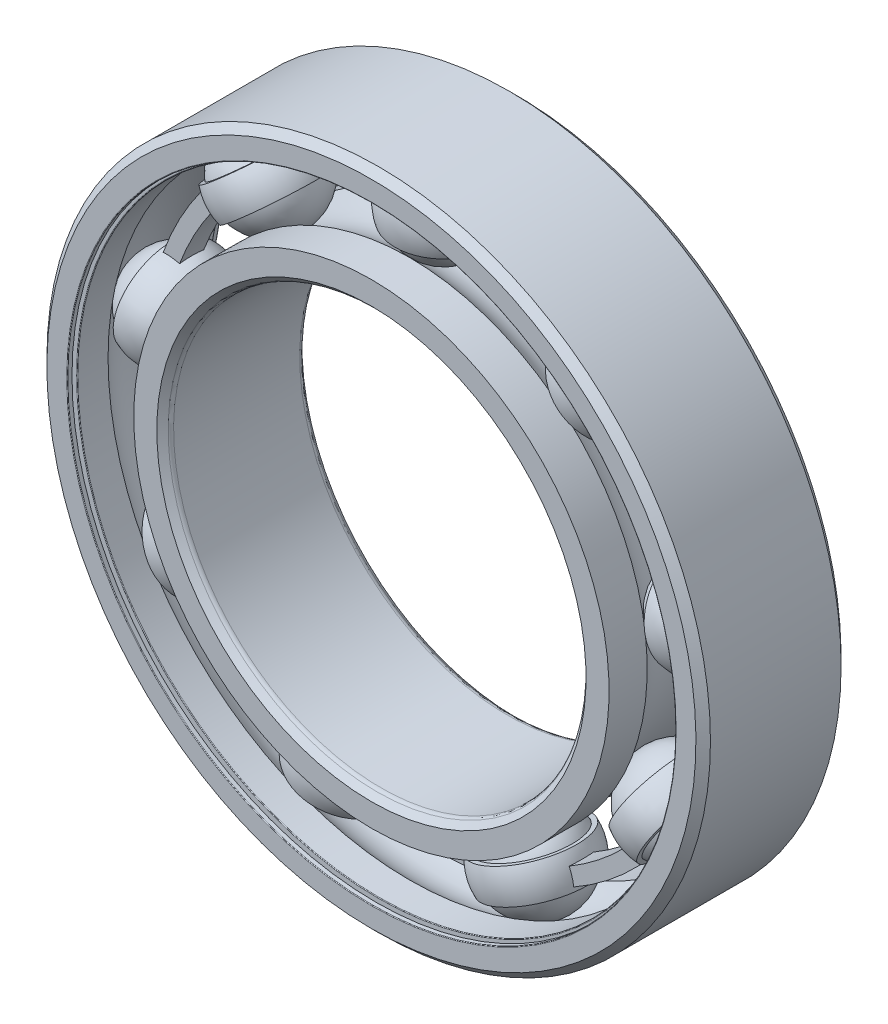
SolidWorks part; units mm, degrees
ref_plane "Front Plane" through (0, 0, 0) normal (0, 0, 1) x (1, 0, 0)
ref_plane "Top Plane" through (0, 0, 0) normal (0, 1, 0) x (1, 0, 0)
ref_plane "Right Plane" through (0, 0, 0) normal (1, 0, 0) x (0, 0, -1)
sketch "Sketch1" plane through (0, 0, 0) normal (0, 0, 1) x (1, 0, 0)
  line L0 (-16, 0) -> (16, 0) construction
  line L1 (-10, 0) -> (10, 0) construction
  circle A0 centre (0, 0) radius 10 construction
  circle A1 centre (0, 0) radius 16 construction
  point P3 (0, 0)
  point P6 (0, 0)
  point P7 (0, -10)
  point P11 (0, -16)
  point P12 (0, 10)
  point P13 (0, 16)
  dimension "OD" = 32
  dimension "ID" = 20
sketch "Sketch2" plane through (0, 0, 0) normal (1, 0, 0) x (0, 0, -1)
  line L0 (-3.5, 16) -> (3.5, 16) construction
  line L1 (0, 16) -> (0, -16) construction
  line L2 (3.15, 16) -> (-3.15, 16)
  line L3 (-3.15, 16) -> (-3.5, 15.65)
  line L4 (-3.5, 15.65) -> (-3.5, 14.5385)
  line L5 (-3.5, 14.5385) -> (-1.6625, 14.5385)
  line L6 (3.5, 14.5385) -> (1.6625, 14.5385)
  line L7 (3.5, 15.65) -> (3.5, 14.5385)
  line L8 (3.15, 16) -> (3.5, 15.65)
  line L9 (0, 16) -> (0, 13) construction
  line L10 (0, 13) -> (0, 10) construction
  line L11 (0, 16) -> (0, -16) construction
  line L12 (-3.5, 0) -> (3.5, 0) construction
  line L13 (3.5, 10) -> (-3.5, 10) construction
  line L14 (0, 15.2651) -> (0, 10.7349) construction
  line L15 (-3.5, -10) -> (3.5, -10) construction
  line L16 (-3.5, -10) -> (-3.5, 10) construction
  line L17 (3.5, 16) -> (3.5, -16) construction
  arc A0 (-1.6625, 14.5385) -> (1.6625, 14.5385) centre (0, 13) cw
  circle A1 centre (0, 13) radius 2.2651 construction
  point P14 (0, 10)
  point P17 (0, 0)
  point P21 (0, 16)
  point P29 (0, 10)
  point P30 (0, -10)
  point P35 (0, 15.2651)
  dimension "Approx. Ball Dia." = 4.5302
  dimension "Width" = 7
  dimension "D1" = 45
  dimension "D2" = 0.35
  dimension "D3" = 3.325
  dimension "D4" = 1.5385
  dimension "For Shaft Diameter" = 20
  dimension "For Housing ID" = 32
sketch "Sketch3" plane through (0, 0, 0) normal (1, 0, 0) x (0, 0, -1)
  line L0 (3.15, 16) -> (3.5, 15.65) construction
  line L1 (3.5, 15.65) -> (3.5, 14.5385) construction
  line L2 (3.5, 14.5385) -> (1.6625, 14.5385) construction
  line L3 (-3.5, 14.5385) -> (-1.6625, 14.5385) construction
  line L4 (-3.5, 15.65) -> (-3.5, 14.5385) construction
  line L5 (-3.15, 16) -> (-3.5, 15.65) construction
  line L6 (3.15, 16) -> (-3.15, 16) construction
  line L7 (3.15, 16) -> (3.5, 15.65)
  line L8 (3.5, 15.65) -> (3.5, 14.5385)
  line L9 (3.5, 14.5385) -> (1.6625, 14.5385)
  line L10 (-3.5, 14.5385) -> (-1.6625, 14.5385)
  line L11 (-3.5, 15.65) -> (-3.5, 14.5385)
  line L12 (-3.15, 16) -> (-3.5, 15.65)
  line L13 (3.15, 16) -> (-3.15, 16)
  arc A0 (1.6625, 14.5385) -> (-1.6625, 14.5385) centre (0, 13) ccw construction
  arc A1 (1.6625, 14.5385) -> (-1.6625, 14.5385) centre (0, 13) ccw
revolve "Revolve1" add sketch "Sketch3" angle 360 about L12
sketch "Sketch8" plane through (0, 0, 0) normal (1, 0, 0) x (0, 0, -1)
  line L0 (-3.5, 14.5385) -> (-1.6625, 14.5385) construction
  line L1 (-3.276, 14.5385) -> (-3.15, 14.5385)
  line L2 (-3.276, 14.5385) -> (-3.276, 15.0256) construction
  line L3 (-3.276, 15.0256) -> (-3.15, 15.0256)
  line L4 (-3.15, 14.5385) -> (-3.15, 15.0256)
  line L5 (3.5, 14.5385) -> (1.6625, 14.5385) construction
  line L6 (3.15, 14.5385) -> (3.276, 14.5385)
  line L7 (3.15, 14.5385) -> (3.15, 15.0256)
  line L8 (3.15, 15.0256) -> (3.276, 15.0256)
  line L9 (3.276, 14.5385) -> (3.276, 15.0256) construction
  line L10 (-3.15, 15.0256) -> (3.15, 15.0256) construction
  line L11 (0, 16) -> (0, -16) construction
  line L12 (-3.276, 15.0256) -> (-3.276, 15.5128) construction
  line L13 (-3.276, 15.5128) -> (-3.276, 16) construction
  line L14 (-3.5, 16) -> (3.5, 16) construction
  line L15 (-3.276, 14.5385) -> (-3.5, 14.5385)
  line L16 (-3.5, 14.5385) -> (-3.5, 14.6645)
  line L17 (-3.5, 15.65) -> (-3.5, 14.5385) construction
  line L18 (-3.5, 14.6645) -> (-3.276, 14.6645)
  line L19 (-3.276, 14.6645) -> (-3.276, 15.0256)
  line L20 (3.276, 14.5385) -> (3.5, 14.5385)
  line L21 (3.5, 14.5385) -> (3.5, 14.6645)
  line L22 (3.5, 15.65) -> (3.5, 14.5385) construction
  line L23 (3.5, 14.6645) -> (3.276, 14.6645)
  line L24 (3.276, 14.6645) -> (3.276, 15.0256)
  point P12 (0, 15.0256)
  dimension "D1" = 6.3
  dimension "D2" = 0.126
revolve "Cut-Revolve1" cut sketch "Sketch8" angle 360 about L12
sketch "Sketch4" plane through (0, 0, 0) normal (1, 0, 0) x (0, 0, -1)
  line L0 (0, 16) -> (0, -16) construction
  line L1 (0, 16) -> (0, -16) construction
  line L2 (-3.15, 10) -> (-3.5, 10.35)
  line L3 (-3.5, 10.35) -> (-3.5, 11.4615)
  line L5 (-3.5, 11.4615) -> (-1.6625, 11.4615)
  line L6 (-3.15, 10) -> (3.15, 10)
  line L8 (3.15, 10) -> (3.5, 10.35)
  line L10 (3.5, 10.35) -> (3.5, 11.4615)
  line L11 (3.5, 11.4615) -> (1.6625, 11.4615)
  line L12 (-3.5, 15.65) -> (-3.5, 14.5385) construction
  line L13 (3.15, 16) -> (3.5, 15.65) construction
  line L15 (3.5, -15.65) -> (3.5, 15.65) construction
  line L16 (3.15, 16) -> (3.15, -16) construction
  arc A1 (1.6625, 11.4615) -> (-1.6625, 11.4615) centre (0, 13) cw
  circle A2 centre (0, 13) radius 2.2651 construction
  point P1 (0, 10)
revolve "Revolve2" add sketch "Sketch4" angle 360 about L12
sketch "Sketch5" plane through (0, 0, 0) normal (1, 0, 0) x (0, 0, -1)
  line L0 (-2.2651, 13) -> (2.2651, 13)
  arc A2 (-2.2651, 13) -> (2.2651, 13) centre (0, 13) cw
  arc A3 (1.6625, 14.5385) -> (-1.6625, 14.5385) centre (0, 13) ccw construction
revolve "Revolve3" add sketch "Sketch5" angle 360 about L0
sketch "Sketch6" plane through (0, 0, 0) normal (1, 0, 0) x (0, 0, -1)
  line L0 (-1.6625, 14.5385) -> (-1.6625, 13.7692) construction
  line L1 (-1.6625, 13.7692) -> (-1.6625, 13) construction
  line L2 (-1.6625, 13) -> (-1.6625, 12.2308) construction
  line L3 (-1.6625, 12.2308) -> (-1.6625, 11.4615) construction
  line L4 (-3.5, 13.7692) -> (-3.2718, 13.7692) construction
  line L5 (-1.6625, 13.7692) -> (-1.6625, 12.2308) construction
  line L7 (-3.2718, 13.7692) -> (-3.0435, 13.7692) construction
  line L8 (-3.0435, 13.7692) -> (-2.8153, 13.7692) construction
  line L10 (0, 16) -> (0, -16) construction
  line L11 (0, 16) -> (0, -16) construction
  line L12 (-3.5, 14.5385) -> (-3.5, 13.7692) construction
  line L13 (-2.3588, 13.7692) -> (-2.1305, 13.7692) construction
  line L14 (-3.5, 15.65) -> (-3.5, -15.65) construction
  line L15 (-3.5, 13.7692) -> (-3.5, 13) construction
  line L16 (-3.5, 13) -> (-3.5, 12.2308) construction
  line L17 (-3.5, 12.2308) -> (-3.5, 11.4615) construction
  line L18 (-2.8153, 13.7692) -> (-2.587, 13.7692) construction
  line L19 (-2.587, 13.7692) -> (-2.3588, 13.7692) construction
  line L20 (-2.1305, 13.7692) -> (-2.3588, 13.7692)
  line L21 (-3.5, 12.2308) -> (-3.2718, 12.2308) construction
  line L22 (-3.2718, 12.2308) -> (-3.0435, 12.2308) construction
  line L23 (-3.0435, 12.2308) -> (-2.8153, 12.2308) construction
  line L24 (-2.8153, 12.2308) -> (-2.587, 12.2308) construction
  line L25 (-2.587, 12.2308) -> (-2.3588, 12.2308) construction
  line L26 (-2.3588, 12.2308) -> (-2.1305, 12.2308) construction
  line L27 (-2.1305, 12.2308) -> (-2.3588, 12.2308)
  line L28 (-2.587, 13.7692) -> (-2.587, 12.2308) construction
  line L30 (-2.4729, 13.7692) -> (-2.4729, 12.2308) construction
  circle A0 centre (0, 13) radius 2.2651 construction
  arc A2 (-2.3588, 12.2308) -> (-2.3588, 13.7692) centre (0.1766, 13) cw
  arc A3 (-2.1305, 13.7692) -> (-2.1305, 12.2308) centre (0, 13) ccw
revolve "Revolve4" add sketch "Sketch6" angle 360 about L11
sketch "Sketch7" plane through (0, 0, 0) normal (0, 0, 1) x (1, 0, 0)
  line L0 (-2.2651, 13) -> (2.2651, 13) construction
  line L1 (0, 10.7349) -> (0, 15.2651) construction
  line L2 (0, 0) -> (4.5056, 12.1943) construction
  line L8 (0, 16) -> (0, -16) construction
  line L9 (8.4526, 9.8769) -> (8.9528, 10.4613)
  line L10 (0, 16) -> (0, -16) construction
  line L11 (0, 13.7692) -> (0, 13)
  arc A1 (8.4526, 9.8769) -> (0, 13) centre (0, 0) ccw
  arc A2 (8.9528, 10.4613) -> (0, 13.7692) centre (0, 0) ccw
  dimension "D1" = 40.557
  dimension "D2" = 4.5302
extrude "Boss-Extrude1" add sketch "Sketch7" along normal mid plane 1.1667
pattern_circular "CirPattern1" count 9 over 360 about axis through (0, 0, 3.5) along (0, 0, -1) of bodies 104 134
pattern_circular "CirPattern2" count 9 over 360 about axis through (0, 0, 3.5) along (0, 0, -1) of "Revolve4", "Boss-Extrude1" reverse direction yes
fillet "Fillet1" radius 0.0315 4 edges at (0, -14.5385, -3.15) (0, -14.6645, -3.5) (0, -14.5385, 3.15) (0, -14.6645, 3.5)
fillet "Fillet2" radius 0.2625 2 edges at (0, -10, -3.15) (0, -10, 3.15)
ref_plane "Plane1" through (4.5056, 12.1943, 0) normal (0.3466, 0.938, 0) x (0.938, -0.3466, 0)
sketch "Sketch9" plane through (4.5056, 12.1943, 0) normal (0.3466, 0.938, 0) x (0.938, -0.3466, 0)
  line L0 (-2.3808, -0.5833) -> (-2.3808, -1.75)
  line L1 (-2.3808, -1.75) -> (-1.0327, -1.75)
  line L2 (-1.0327, -1.75) -> (0, -0.8834)
  line L3 (0, -0.8834) -> (1.0327, -1.75)
  line L4 (1.0327, -1.75) -> (2.3808, -1.75)
  line L5 (2.3808, -1.75) -> (2.3808, -0.5833)
  line L6 (2.3808, -0.5833) -> (-2.3808, -0.5833)
  line L7 (0, -0.5833) -> (0, 0) construction
  line L8 (-2.3808, -0.5833) -> (-2.3808, 0) construction
  dimension "D1" = 1.1667
  dimension "D2" = 0.5833
  dimension "D3" = 40
extrude "Boss-Extrude2" [suppressed] add sketch "Sketch9" along normal blind 1.982 draft 15 and the other way blind 1.982 draft 10 separate body draft outward yes other way draft outward yes
fillet "Fillet3" [suppressed] radius 0.35
mirror "Mirror1" [suppressed] about plane through (0, 0, 0) normal (0, 0, 1) of bodies 149
pattern_circular "CirPattern3" [suppressed] count 9 over 360 about axis through (0, 0, 3.5) along (0, 0, -1) of bodies 158 149
equation "\"D2@Sketch2\" = \"Width@Sketch2\" * .05"
equation "\"D3@Sketch2\"=\"Width@Sketch2\" * .475"
equation "\"D4@Sketch2\" =  (  (  ( \"OD@Sketch1\" - \"Width@Sketch2\" )  / 2 )  / 3.25 )  / 2.5"
equation "\"D1@Boss-Extrude1\" = \"Width@Sketch2\" / 6"
equation "\"D1@Sketch8\"=\"Width@Sketch2\"*.9"
equation "\"D2@Sketch8\"=\"D1@Sketch8\"*.02"
equation "\"D1@Fillet1\" = \"D2@Sketch8\" * .25"
equation "\"D1@Fillet2\" = \"D2@Sketch2\" * .75"
equation "\"Approx No of Balls\"= ( pi * \"OD@Sketch1\" ) * .4 / \"Approx. Ball Dia.@Sketch2\""
equation "\"D1@CirPattern1\"=\"Approx No of Balls\""
equation "\"D1@Sketch7\"=360/\"Approx No of Balls\""
equation "\"D1@CirPattern2\"=\"Approx No of Balls\""
equation "\"D2@Sketch7\"=\"Approx. Ball Dia.@Sketch2\""
equation "\"D2@Sketch9\"=\"d1@boss-extrude1\"*.5"
equation "\"D1@Sketch9\"=\"D2@Sketch9\"*2"
equation "\"D1@Boss-Extrude2\"=\"Approx. Ball Dia.@Sketch2\"*.4375"
equation "\"D2@Boss-Extrude2\"=\"D1@Boss-Extrude2\""
equation "\"D1@CirPattern3\"=\"Approx No of Balls\""
equation "\"D1@Fillet3\"=\"D1@Sketch9\" * .3"
